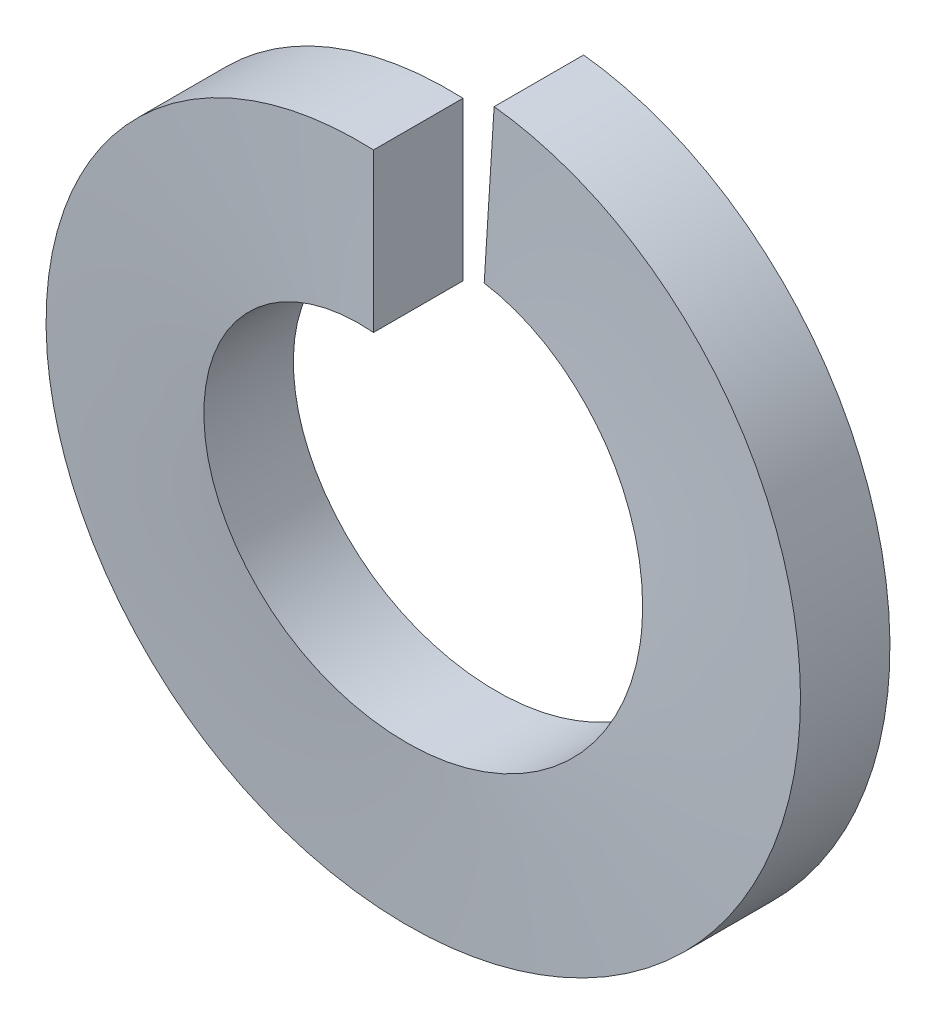
SolidWorks part; units mm, degrees
ref_plane "Front Plane" through (0, 0, 0) normal (0, 0, 1) x (1, 0, 0)
ref_plane "Top Plane" through (0, 0, 0) normal (0, 1, 0) x (1, 0, 0)
ref_plane "Right Plane" through (0, 0, 0) normal (1, 0, 0) x (0, 0, -1)
sketch "Sketch1" plane through (0, 0, 0) normal (0, 0, 1) x (1, 0, 0)
  line L0 (0, 5.9) -> (0, 3.25) construction
  circle A0 centre (0, 0) radius 5.9
  circle A1 centre (0, 0) radius 3.25 construction
  dimension "ID" = 6.5
  dimension "OD" = 11.8
curve "Helix/Spiral1" pitch 1.6667 height 1.65 radius 5.9 left hand yes centre (0, 0, 0) axis (0, 0, -1) start towards (0, 1, 0) parameters "HT"=1.65
sketch "Sketch2" plane through (0, 0, 0) normal (1, 0, 0) x (0, 0, -1)
  line L1 (0, 5.9) -> (-1.5, 5.9)
  line L2 (0, 5.9) -> (0, 3.25)
  line L3 (0, 3.25) -> (-1.5, 3.25)
  line L4 (-1.5, 5.9) -> (-1.5, 3.25)
  dimension "THK" = 1.5
sweep "Sweep1" add profiles "Sketch2" path "Helix/Spiral1"
ref_axis "Axis1" through (0, 0, 1.7289) along (0, 0, -1)
equation "\"HT@Helix/Spiral1\" = \"THK@Sketch2\"*1.1"
